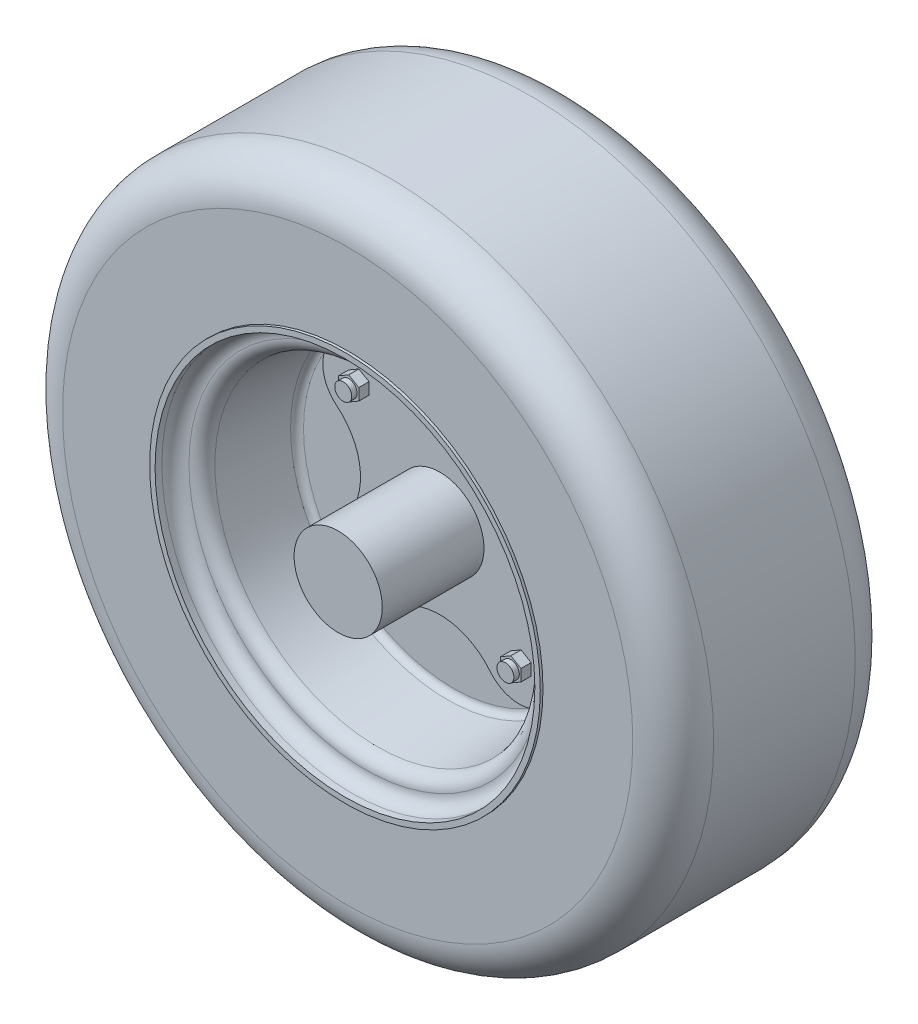
SolidWorks part; units mm, degrees
material "Rubber"
ref_plane "Front Plane" through (0, 0, 0) normal (0, 0, 1) x (1, 0, 0)
ref_plane "Top Plane" through (0, 0, 0) normal (0, 1, 0) x (1, 0, 0)
ref_plane "Right Plane" through (0, 0, 0) normal (1, 0, 0) x (0, 0, -1)
sketch "Sketch4" plane through (0, 0, 0) normal (0, 0, 1) x (1, 0, 0)
  line L0 (0, -6.35) -> (0, -27.1526) construction
  line L1 (0, -27.1526) -> (43.18, -27.1526)
  line L2 (43.18, -27.1526) -> (43.18, -16.0401)
  line L3 (43.18, -16.0401) -> (40.64, -16.0401)
  line L4 (40.64, -16.0401) -> (40.64, -13.5001)
  line L5 (40.64, -13.5001) -> (44.45, -13.5001)
  line L6 (44.45, -13.5001) -> (44.45, -6.35)
  line L7 (44.45, -6.35) -> (0, -6.35)
  line L9 (0, -6.35) -> (0, -27.1526)
  line L10 (-127.4196, -221.8568) -> (-28.4907, -27.1526) construction
  line L11 (-82.1304, -244.8682) -> (28.4907, -27.1526) construction
  line L12 (-104.775, -233.3625) -> (0, -27.1526) construction
  line L13 (0, 0) -> (0, -385.7625) construction
  circle A0 centre (-104.775, -233.3625) radius 152.4 construction
  arc A1 (-127.4196, -221.8568) -> (-82.1304, -244.8682) centre (-104.775, -233.3625) ccw construction
  point P13 (-104.775, -80.9625)
  point P14 (-104.775, -385.7625)
  dimension "Wheel Dia" = 304.8
  dimension "D7" = 50.8
  dimension "Mount Height" = 385.7625
  dimension "Offset" = 104.775
  dimension "D1" = 7.1501
  dimension "D2" = 11.1125
  dimension "D3" = 2.54
  dimension "D4" = 88.9
  dimension "D5" = 86.36
  dimension "D6" = 81.28
revolve "Revolve1" [suppressed] add sketch "Sketch4" angle 360 about L0
ref_plane "Plane1" through (-104.775, 0, 0) normal (1, 0, 0) x (0, 0, -1)
sketch "Sketch5" plane through (-104.775, 0, 0) normal (1, 0, 0) x (0, 0, -1)
  line L1 (-52.07, -80.9625) -> (52.07, -80.9625)
  line L2 (-52.07, -80.9625) -> (-52.07, -385.7625)
  line L3 (-52.07, -385.7625) -> (52.07, -385.7625)
  line L4 (52.07, -80.9625) -> (52.07, -385.7625)
  dimension "Wheel Width" = 104.14
sketch "Sketch6" plane through (-104.775, 0, 0) normal (1, 0, 0) x (0, 0, -1)
  line L0 (-52.07, -141.9225) -> (-52.07, -99.897)
  line L1 (-33.1355, -80.9625) -> (-28.9935, -80.9625)
  line L2 (52.07, -99.897) -> (52.07, -141.9225)
  line L3 (-52.07, -80.9625) -> (52.07, -80.9625) construction
  line L4 (-52.07, -80.9625) -> (-52.07, -385.7625) construction
  line L5 (52.07, -80.9625) -> (52.07, -385.7625) construction
  line L6 (-111.1453, -233.3625) -> (111.1453, -233.3625) construction
  line L7 (-52.07, -141.9225) -> (-53.34, -141.9225)
  line L8 (-53.34, -141.9225) -> (-53.34, -144.4625)
  line L9 (-53.34, -212.725) -> (-56.515, -212.725)
  line L10 (-56.515, -212.725) -> (-56.515, -233.3625)
  line L11 (0, -80.9625) -> (0, -256.5466) construction
  line L12 (0, -80.9625) -> (0, -385.7625) construction
  line L13 (56.515, -212.725) -> (56.515, -233.3625)
  line L14 (53.34, -212.725) -> (56.515, -212.725)
  line L15 (28.9935, -80.9625) -> (20.7097, -80.9625)
  line L16 (12.4258, -80.9625) -> (4.1419, -80.9625)
  line L17 (-56.515, -233.3625) -> (56.515, -233.3625)
  line L18 (-28.9935, -80.9625) -> (-28.9935, -83.3438) construction
  line L19 (-28.9935, -83.3438) -> (-20.7097, -83.3438) construction
  line L20 (-20.7097, -83.3438) -> (-20.7097, -80.9625) construction
  line L21 (-12.4258, -80.9625) -> (-12.4258, -83.3438) construction
  line L22 (-12.4258, -83.3438) -> (-4.1419, -83.3438) construction
  line L23 (-4.1419, -83.3438) -> (-4.1419, -80.9625) construction
  line L24 (4.1419, -83.3438) -> (4.1419, -80.9625) construction
  line L25 (12.4258, -83.3438) -> (4.1419, -83.3438) construction
  line L26 (12.4258, -80.9625) -> (12.4258, -83.3438) construction
  line L27 (20.7097, -83.3438) -> (20.7097, -80.9625) construction
  line L28 (28.9935, -83.3438) -> (20.7097, -83.3438) construction
  line L29 (28.9935, -80.9625) -> (28.9935, -83.3438) construction
  line L30 (-20.7097, -80.9625) -> (-12.4258, -80.9625)
  line L31 (-4.1419, -80.9625) -> (4.1419, -80.9625)
  line L32 (12.4258, -80.9625) -> (20.7097, -80.9625)
  line L33 (28.9935, -80.9625) -> (33.1355, -80.9625)
  line L34 (-53.34, -144.4625) -> (-50.165, -144.4625)
  line L35 (-38.0184, -157.1383) -> (-5.4383, -159.9887)
  line L36 (-2.54, -163.1516) -> (-2.54, -212.725)
  line L37 (-43.815, -150.8125) -> (-43.815, -208.9815) construction
  line L38 (-53.34, -212.725) -> (-2.54, -212.725)
  line L39 (53.34, -212.725) -> (2.54, -212.725)
  line L40 (2.54, -163.1516) -> (2.54, -212.725)
  line L41 (38.0184, -157.1383) -> (5.4383, -159.9887)
  line L42 (53.34, -144.4625) -> (50.165, -144.4625)
  line L43 (53.34, -141.9225) -> (53.34, -144.4625)
  line L44 (52.07, -141.9225) -> (53.34, -141.9225)
  line L45 (-4.1419, -80.9625) -> (-12.4258, -80.9625)
  line L46 (-20.7097, -80.9625) -> (-28.9935, -80.9625)
  arc A0 (-52.07, -99.897) -> (-33.1355, -80.9625) centre (-33.1355, -99.897) cw
  arc A1 (33.1355, -80.9625) -> (52.07, -99.897) centre (33.1355, -99.897) cw
  arc A2 (-50.165, -144.4625) -> (-43.815, -150.8125) centre (-50.165, -150.8125) cw
  arc A3 (-43.815, -150.8125) -> (-38.0184, -157.1383) centre (-37.465, -150.8125) ccw
  arc A4 (-5.4383, -159.9887) -> (-2.54, -163.1516) centre (-5.715, -163.1516) cw
  arc A5 (5.4383, -159.9887) -> (2.54, -163.1516) centre (5.715, -163.1516) ccw
  arc A6 (43.815, -150.8125) -> (38.0184, -157.1383) centre (37.465, -150.8125) cw
  arc A7 (50.165, -144.4625) -> (43.815, -150.8125) centre (50.165, -150.8125) ccw
  dimension "D1" = 18.9345
  dimension "D13" = 6.35
  dimension "D16" = 3.175
  dimension "D2" = 1.27
  dimension "D3" = 3.175
  dimension "D4" = 41.275
  dimension "D5" = 182.88
  dimension "D6" = 66.2709
  dimension "D7" = 8.2839
  dimension "D8" = 2.3813
  dimension "D9" = 8.2839
  dimension "D10" = 4.1419
  dimension "D11" = 3.175
  dimension "D12" = 2.54
  dimension "D14" = 5
  dimension "D15" = 2.54
revolve "Revolve2" add sketch "Sketch6" angle 360 about L6
sketch "Sketch13" plane through (0, 0, 2.54) normal (0, 0, 1) x (1, 0, 0)
  line L0 (-104.775, -212.725) -> (-104.775, -163.1516) construction
  line L1 (-104.775, -233.3625) -> (-154.4216, -183.7159) construction
  line L2 (-104.775, -233.3625) -> (-60.3899, -233.3625) construction
  circle A0 centre (-104.775, -233.3625) radius 70.2109 construction
  circle A1 centre (-104.775, -233.3625) radius 20.6375
  circle A2 centre (-104.775, -233.3625) radius 20.6375 construction
  circle A4 centre (-104.775, -233.3625) radius 70.2109 construction
  circle A6 centre (-104.775, -233.3625) radius 37.162 construction
  circle A7 centre (-104.775, -233.3625) radius 53.6864 construction
  arc A8 (-153.0787, -209.9321) -> (-128.2054, -185.0588) centre (-141.9195, -196.218) cw
  arc A9 (-128.2054, -185.0588) -> (-81.3446, -185.0588) centre (-104.775, -165.9934) ccw
  arc A10 (-81.3446, -185.0588) -> (-56.4713, -209.9321) centre (-67.6305, -196.218) cw
  arc A11 (-153.0787, -209.9321) -> (-153.0787, -256.7929) centre (-172.1441, -233.3625) cw
  arc A12 (-56.4713, -209.9321) -> (-56.4713, -256.7929) centre (-37.4059, -233.3625) ccw
  arc A13 (-153.0787, -256.7929) -> (-128.2054, -281.6662) centre (-141.9195, -270.507) ccw
  arc A15 (-81.3446, -281.6662) -> (-56.4713, -256.7929) centre (-67.6305, -270.507) ccw
  arc A16 (-128.2054, -281.6662) -> (-81.3446, -281.6662) centre (-104.775, -300.7316) cw
  point P8 (-104.775, -196.2005)
  point P9 (-104.775, -179.6761)
  dimension "D2" = 49.5734
  dimension "D3" = 16.5245
  dimension "D4" = 16.5245
  dimension "D5" = 45
extrude "Boss-Extrude5" add sketch "Sketch13" along normal blind 6.35
sketch "Sketch14" plane through (0, 0, 8.89) normal (0, 0, 1) x (1, 0, 0)
  line L0 (-104.775, -233.3625) -> (-154.4216, -183.7159) construction
  line L1 (-142.737, -200.8997) -> (-137.9745, -198.1501)
  line L2 (-137.9745, -198.1501) -> (-137.9745, -192.6509)
  line L3 (-137.9745, -192.6509) -> (-142.737, -189.9012)
  line L4 (-142.737, -189.9012) -> (-147.4995, -192.6509)
  line L5 (-147.4995, -192.6509) -> (-147.4995, -198.1501)
  line L6 (-147.4995, -198.1501) -> (-142.737, -200.8997)
  line L7 (-104.775, -233.3625) -> (-104.775, -136.2548) construction
  line L8 (-104.775, -233.3625) -> (-63.5, -233.3625) construction
  line L9 (-62.0505, -198.1501) -> (-66.813, -200.8997)
  line L10 (-62.0505, -192.6509) -> (-62.0505, -198.1501)
  line L11 (-66.813, -189.9012) -> (-62.0505, -192.6509)
  line L12 (-71.5755, -192.6509) -> (-66.813, -189.9012)
  line L13 (-71.5755, -198.1501) -> (-71.5755, -192.6509)
  line L14 (-66.813, -200.8997) -> (-71.5755, -198.1501)
  line L15 (-66.813, -265.8253) -> (-71.5755, -268.5749)
  line L16 (-71.5755, -268.5749) -> (-71.5755, -274.0741)
  line L17 (-71.5755, -274.0741) -> (-66.813, -276.8238)
  line L18 (-66.813, -276.8238) -> (-62.0505, -274.0741)
  line L19 (-62.0505, -274.0741) -> (-62.0505, -268.5749)
  line L20 (-62.0505, -268.5749) -> (-66.813, -265.8253)
  line L21 (-147.4995, -268.5749) -> (-142.737, -265.8253)
  line L22 (-147.4995, -274.0741) -> (-147.4995, -268.5749)
  line L23 (-142.737, -276.8238) -> (-147.4995, -274.0741)
  line L24 (-137.9745, -274.0741) -> (-142.737, -276.8238)
  line L25 (-137.9745, -268.5749) -> (-137.9745, -274.0741)
  line L26 (-142.737, -265.8253) -> (-137.9745, -268.5749)
  circle A0 centre (-142.737, -195.4005) radius 4.7625 construction
  circle A1 centre (-104.775, -233.3625) radius 53.6864 construction
  circle A3 centre (-66.813, -195.4005) radius 4.7625 construction
  circle A4 centre (-66.813, -271.3245) radius 4.7625 construction
  circle A5 centre (-142.737, -271.3245) radius 4.7625 construction
  dimension "D1" = 9.525
extrude "Boss-Extrude6" add sketch "Sketch14" along normal blind 4.7625
sketch "Sketch15" plane through (0, 0, 13.6525) normal (0, 0, 1) x (1, 0, 0)
  circle A0 centre (-142.737, -195.4005) radius 3.9687
  circle A1 centre (-66.813, -195.4005) radius 3.9687
  circle A2 centre (-142.737, -271.3245) radius 3.9687
  circle A3 centre (-66.813, -271.3245) radius 3.9687
  dimension "D1" = 7.9375
extrude "Boss-Extrude7" add sketch "Sketch15" along normal blind 2.54
sketch "Sketch16" plane through (0, 0, -2.54) normal (0, 0, -1) x (-1, 0, 0)
  circle A0 centre (66.813, -195.4005) radius 6.35
  circle A1 centre (142.737, -195.4005) radius 6.35
  circle A2 centre (142.737, -271.3245) radius 6.35
  circle A3 centre (66.813, -271.3245) radius 6.35
  dimension "D1" = 12.7
extrude "Boss-Extrude8" add sketch "Sketch16" along normal blind 4.7625
sketch "Sketch7" [suppressed] plane through (0, -27.1526, 0) normal (0, -1, 0) x (1, 0, 0)
  line L0 (-84.1375, 56.515) -> (-125.4125, 56.515) construction
  line L1 (-257.175, 65.405) -> (28.4907, 65.405)
  line L2 (-257.175, 65.405) -> (-257.175, -65.405)
  line L3 (-257.175, -65.405) -> (28.4907, -65.405)
  line L4 (28.4907, 65.405) -> (28.4907, -65.405)
  line L6 (-257.175, 33.1355) -> (-257.175, -33.1355) construction
  line L8 (28.4907, -65.405) -> (28.4907, 65.405) construction
  line L9 (-28.4907, 65.405) -> (-28.4907, -65.405) construction
  line L14 (-28.4907, 32.4468) -> (28.4907, 32.4468) construction
  line L15 (-28.4907, 32.4468) -> (-28.4907, 26.0968) construction
  line L16 (-28.4907, 26.0968) -> (28.4907, 26.0968) construction
  line L17 (28.4907, 32.4468) -> (28.4907, 26.0968) construction
  line L18 (-28.4907, -26.0968) -> (28.4907, -26.0968) construction
  line L19 (-28.4907, -26.0968) -> (-28.4907, -32.4468) construction
  line L20 (-28.4907, -32.4468) -> (28.4907, -32.4468) construction
  line L21 (28.4907, -26.0968) -> (28.4907, -32.4468) construction
  circle A0 centre (0, 0) radius 43.18 construction
  circle A1 centre (0, 0) radius 43.18 construction
  dimension "D1" = 8.89
  dimension "D3" = 6.35
extrude "Boss-Extrude2" [suppressed] add sketch "Sketch7" along normal up to vertex separate body
sketch "Sketch8" [suppressed] plane through (0, 0, 65.405) normal (0, 0, 1) x (1, 0, 0)
  line L0 (-127.4196, -221.8568) -> (-28.4907, -27.1526) construction
  line L1 (-82.1304, -244.8682) -> (28.4907, -27.1526) construction
  line L2 (-127.4196, -221.8568) -> (-28.4907, -27.1526)
  line L3 (-82.1304, -244.8682) -> (28.4907, -27.1526)
  arc A0 (-127.4196, -221.8568) -> (-82.1304, -244.8682) centre (-104.775, -233.3625) ccw construction
  arc A1 (-127.4196, -221.8568) -> (-82.1304, -244.8682) centre (-104.775, -233.3625) ccw
extrude "Cut-Extrude1" [suppressed] cut sketch "Sketch8" against normal through all and the other way through all flip side to cut
sketch "Sketch9" [suppressed] plane through (0, -144.3067, 0) normal (-1, 0, 0) x (0, 0, -1)
  line L0 (65.405, 241.4558) -> (65.405, -63.3442)
  line L2 (65.405, -117.1541) -> (-65.405, -117.1541) construction
  line L3 (26.0968, -117.1541) -> (59.055, -63.3442)
  line L4 (26.0968, -117.1541) -> (32.4468, -117.1541) construction
  line L5 (59.055, -63.3442) -> (59.055, 241.4558)
  line L6 (65.405, 241.4558) -> (59.055, 241.4558)
  line L7 (65.405, -117.1541) -> (65.405, 100.5615) construction
  line L8 (-52.07, 241.4558) -> (52.07, 241.4558) construction
  line L9 (65.405, -63.3442) -> (32.4468, -117.1541)
  line L10 (26.0968, -117.1541) -> (32.4468, -117.1541)
  line L11 (0, -144.3067) -> (0, 241.4558) construction
  line L12 (-26.0968, -117.1541) -> (-32.4468, -117.1541)
  line L13 (-65.405, -63.3442) -> (-32.4468, -117.1541)
  line L14 (-65.405, 241.4558) -> (-59.055, 241.4558)
  line L15 (-59.055, -63.3442) -> (-59.055, 241.4558)
  line L16 (-26.0968, -117.1541) -> (-59.055, -63.3442)
  line L17 (-65.405, 241.4558) -> (-65.405, -63.3442)
  dimension "D1" = 6.35
  dimension "D2" = 6.35
extrude "Cut-Extrude3" [suppressed] cut sketch "Sketch9" against normal through all and the other way through all flip side to cut
sketch "Sketch10" [suppressed] plane through (0, 0, 65.405) normal (0, 0, 1) x (1, 0, 0)
  line L1 (-104.775, -220.5309) -> (-115.8875, -226.9467)
  line L2 (-115.8875, -226.9467) -> (-115.8875, -239.7783)
  line L3 (-115.8875, -239.7783) -> (-104.775, -246.1941)
  line L4 (-104.775, -246.1941) -> (-93.6625, -239.7783)
  line L5 (-93.6625, -239.7783) -> (-93.6625, -226.9467)
  line L6 (-93.6625, -226.9467) -> (-104.775, -220.5309)
  circle A0 centre (-104.775, -233.3625) radius 11.1125 construction
  dimension "D1" = 22.225
extrude "Boss-Extrude3" [suppressed] add sketch "Sketch10" along normal blind 7.9375 separate body
sketch "Sketch11" [suppressed] plane through (0, 0, 73.3425) normal (0, 0, 1) x (1, 0, 0)
  circle A0 centre (-104.775, -233.3625) radius 11.1125 construction
  circle A1 centre (-104.775, -233.3625) radius 11.1125
extrude "Cut-Extrude4" [suppressed] cut sketch "Sketch11" against normal through all draft 60 flip side to cut
mirror "Mirror1" [suppressed] about plane through (0, 0, 0) normal (0, 0, 1) of bodies 113
sketch "Sketch12" [suppressed] plane through (0, 0, -59.055) normal (0, 0, 1) x (1, 0, 0)
  circle A0 centre (-104.775, -233.3625) radius 10.795
  dimension "D1" = 21.59
extrude "Boss-Extrude4" [suppressed] add sketch "Sketch12" along normal up to surface (118.11 mm away)
ref_axis "Center Axis 1" [suppressed] through (0, -37.5072, 0) along (0, 1, 0)
ref_plane "Plane2" [suppressed] through (18.3991, -223.2093, 0) normal (-0.0822, 0.9966, 0) x (-0.0727, -0.006, 0.9973)
sketch "Sketch17" [suppressed] plane through (18.3991, -223.2093, 0) normal (-0.0822, 0.9966, 0) x (-0.0727, -0.006, 0.9973)
  line L0 (-49.8795, -127.5714) -> (-49.8795, -170.5542) construction
  line L1 (-49.8795, -170.5542) -> (-49.8795, 348.1925) construction
equation "\"D5@Sketch6\" = \"Wheel Dia@Sketch4\"*.6"
equation "\"D1@Sketch6\" = \"Wheel Width@Sketch5\"/5.5"
equation "\"D7@Sketch6\" = \"D6@Sketch6\"/8"
equation "\"D9@Sketch6\" = \"D7@Sketch6\""
equation "\"D10@Sketch6\" = \"D7@Sketch6\"/2"
equation "\"D3@Sketch13\" = \"D2@Sketch13\"/3"
equation "\"D4@Sketch13\" = \"D3@Sketch13\""
